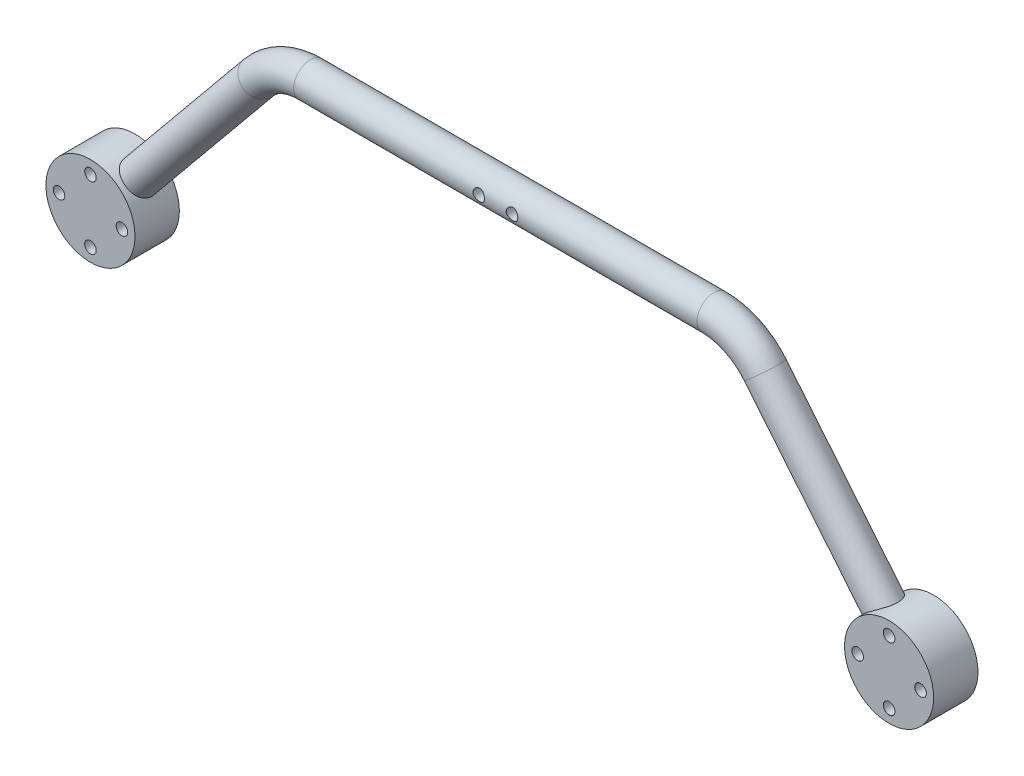
SolidWorks part; units mm, degrees
ref_plane "Front Plane" through (0, 0, 0) normal (0, 0, 1) x (1, 0, 0)
ref_plane "Top Plane" through (0, 0, 0) normal (0, 1, 0) x (1, 0, 0)
ref_plane "Right Plane" through (0, 0, 0) normal (1, 0, 0) x (0, 0, -1)
sketch "Sketch1" plane through (0, 0, 0) normal (0, 0, 1) x (1, 0, 0)
  line L0 (-216.0578, -96.9368) -> (-12.9419, -12.8035)
  line L1 (-216.0578, -96.9368) -> (-206.3377, -120.4034)
  line L2 (-12.9419, -12.8035) -> (-3.2218, -36.27)
  line L3 (-206.3377, -120.4034) -> (-3.2218, -36.27)
  line L4 (12.9419, -12.8035) -> (216.0578, -96.9368)
  line L5 (12.9419, -12.8035) -> (3.2218, -36.27)
  line L6 (216.0578, -96.9368) -> (206.3377, -120.4034)
  line L7 (3.2218, -36.27) -> (206.3377, -120.4034)
  line L8 (-12.9419, -12.8035) -> (0, -7.4427)
  line L9 (0, -7.4427) -> (12.9419, -12.8035)
  line L10 (0, 19.4566) -> (0, -8.1997) construction
  line L11 (-228.6, -115.5981) -> (-228.6, -90.0981) construction
  line L12 (228.6, -115.5981) -> (228.6, -90.0981) construction
  circle A0 centre (-228.6, -115.5981) radius 25.5
  circle A3 centre (-228.6, -115.5981) radius 85.471 construction
  circle A4 centre (228.6, -115.5981) radius 25.5
  circle A5 centre (228.6, -115.5981) radius 85.471 construction
  point P7 (0, 0)
  point P16 (-228.6, -97.5981)
  point P17 (228.6, -97.5981)
  dimension "D5" = 51
  dimension "D6" = 170.942
  dimension "D1" = 135
  dimension "D2" = 25.4
  dimension "D3" = 25.4
  dimension "D4" = 18
  dimension "D7" = 18
  dimension "D8" = 457.2
extrude "Boss-Extrude1" add sketch "Sketch1" along normal blind 25.4 contours L0 A0 L3 L1 | L4 A4 L7 L6 | L3 A0 L0 L1 | L7 A4 L4 L6 region at (-230.1225, -116.2161, 0) region at (-208.5356, -107.4543, 0) region at (230.1225, -116.2161, 0) region at (208.5356, -107.4543, 0)
hole_wizard "M6 Clearance Hole1" positions "3DSketch2" profile "Sketch3" hole size "M6" standard "ANSI Metric" end condition through all
sketch3d "3DSketch2"
  point P2 (-228.6, -97.5981, 0)
sketch "Sketch3" plane through (-228.6, -97.5981, 0) normal (1, 0, 0) x (0, 1, 0)
  line L0 (0, 0) -> (0, 25.4)
  line L1 (0, 25.4) -> (3.3, 25.4)
  line L2 (3.3, 25.4) -> (3.3, 0)
  line L5 (3.3, 0) -> (0, 0)
  line L11 (0, -6.35) -> (0, 107.95) construction
  dimension "Thru Hole Dia." = 6.6
  dimension "Thru Hole Depth" = 25.4
sketch "Sketch26" plane through (0, 0, 25.4) normal (0, 0, 1) x (1, 0, 0)
  point P0 (228.6, -97.5981)
hole_wizard "M6 Clearance Hole3" positions "Sketch26" profile "Sketch27" hole size "M6" standard "ANSI Metric" end condition through all
sketch "Sketch27" plane through (228.6, -97.5981, 25.4) normal (1, 0, 0) x (0, -1, 0)
  line L0 (0, 0) -> (0, 25.4)
  line L1 (0, 25.4) -> (3.3, 25.4)
  line L2 (3.3, 25.4) -> (3.3, 0.025)
  line L3 (3.3, 0.025) -> (3.325, 0)
  line L5 (3.325, 0) -> (0, 0)
  line L6 (-3.3, 0.025) -> (-3.325, 0) construction
  line L11 (0, -6.35) -> (0, 107.95) construction
  dimension "Thru Hole Dia." = 6.6
  dimension "Thru Hole Depth" = 25.4
  dimension "Near C'Sink Dia." = 6.65
  dimension "Near C'Sink Angle" = 90
pattern_circular "CirPattern1" count 4 over 360 about axis through (-228.6, -115.5981, 25.4) along (0, 0, -1) of "M6 Clearance Hole1"
pattern_circular "CirPattern2" count 4 over 360 about axis through (228.6, -115.5981, 25.4) along (0, 0, -1) of "M6 Clearance Hole3"
ref_plane "Plane1" through (0, 0, 12.7) normal (0, 0, 1) x (1, 0, 0)
sketch "Sketch4" plane through (0, 0, 12.7) normal (0, 0, 1) x (1, 0, 0)
  line L0 (-218.4565, -103.4806) -> (-144.8982, -13.9185)
  line L1 (-115.4556, 0) -> (115.4556, 0)
  line L2 (144.8982, -13.9185) -> (218.4565, -103.4806)
  arc A0 (115.4556, 0) -> (144.8982, -13.9185) centre (115.4556, -38.1) cw
  arc A1 (-144.8982, -13.9185) -> (-115.4556, 0) centre (-115.4556, -38.1) cw
  point P5 (0, 0)
  point P6 (-133.4667, 0)
  point P7 (-228.6, -118.1575)
  point P8 (-218.4565, -103.4806)
  dimension "D1" = 38.1
sweep "Sweep1" add path "Sketch4" circular profile diameter 19.05 parameters "D3"=19.05
sketch "Sketch23" plane through (0, 0, 25.4) normal (0, 0, 1) x (1, 0, 0)
  line L0 (-9.525, 0) -> (9.525, 0) construction
  dimension "D1" = 19.05
hole_wizard "M6 Clearance Hole2" positions "3DSketch3" profile "Sketch25" hole size "M6" standard "ANSI Metric" end condition through all
sketch3d "3DSketch3"
  point P0 (-9.525, 0, 22.225)
  point P2 (9.525, 0, 22.225)
  point P5 (0, 0, 0)
sketch "Sketch25" plane through (-9.525, 0, 22.225) normal (1, 0, 0) x (0, -1, 0)
  line L0 (0, 0) -> (0, 22.225)
  line L1 (0, 22.225) -> (3.3, 22.225)
  line L2 (3.3, 22.225) -> (3.3, 0.025)
  line L3 (3.3, 0.025) -> (3.325, 0)
  line L5 (3.325, 0) -> (0, 0)
  line L6 (-3.3, 0.025) -> (-3.325, 0) construction
  line L11 (0, -6.35) -> (0, 107.95) construction
  dimension "Thru Hole Dia." = 6.6
  dimension "Thru Hole Depth" = 22.225
  dimension "Near C'Sink Dia." = 6.65
  dimension "Near C'Sink Angle" = 90
equation "\"Rover_Length\"= 25in"
equation "\"Rover_Width\"= 18in"
equation "\"Rover_Height\"= 12in"
equation "\"Chassis_Wheelbase\"= 18in"
equation "\"Chassis_WheelDiam\"= 171mm"
equation "\"Chassis_ArmDiamWidth\"= 0.75in"
equation "\"Chassis_ArmAngle\"= 135deg"
equation "\"Chassis_HubMountOD\"= \"Chassis_WheelBoltHole\" + 3mm + 12mm"
equation "\"Chassis_WheelBoltHole\"= 36mm"
equation "\"Chassis_WheelBoltNum\"= 4"
equation "\"Chassis_DiffBarLength\"= 12in"
equation "\"Chassis_DiffBarWidth\"= 1in"
equation "\"Chassis_DiffBarHeight\"= 0.5in"
equation "\"Chassis_DiffLinkage_Length\"= 2.5in"
equation "\"D2@Sketch1\"=\"Chassis_DiffBarWidth\""
equation "\"D3@Sketch1\"=\"Chassis_DiffBarWidth\""
equation "\"D5@Sketch1\"=\"Chassis_HubMountOD\""
equation "\"D4@Sketch1\"=\"Chassis_WheelBoltHole\"/2"
equation "\"D7@Sketch1\"=\"Chassis_WheelBoltHole\"/2"
equation "\"D8@Sketch1\"=\"Chassis_Wheelbase\""
equation "\"D1@Boss-Extrude1\"=\"Chassis_DiffBarWidth\""
